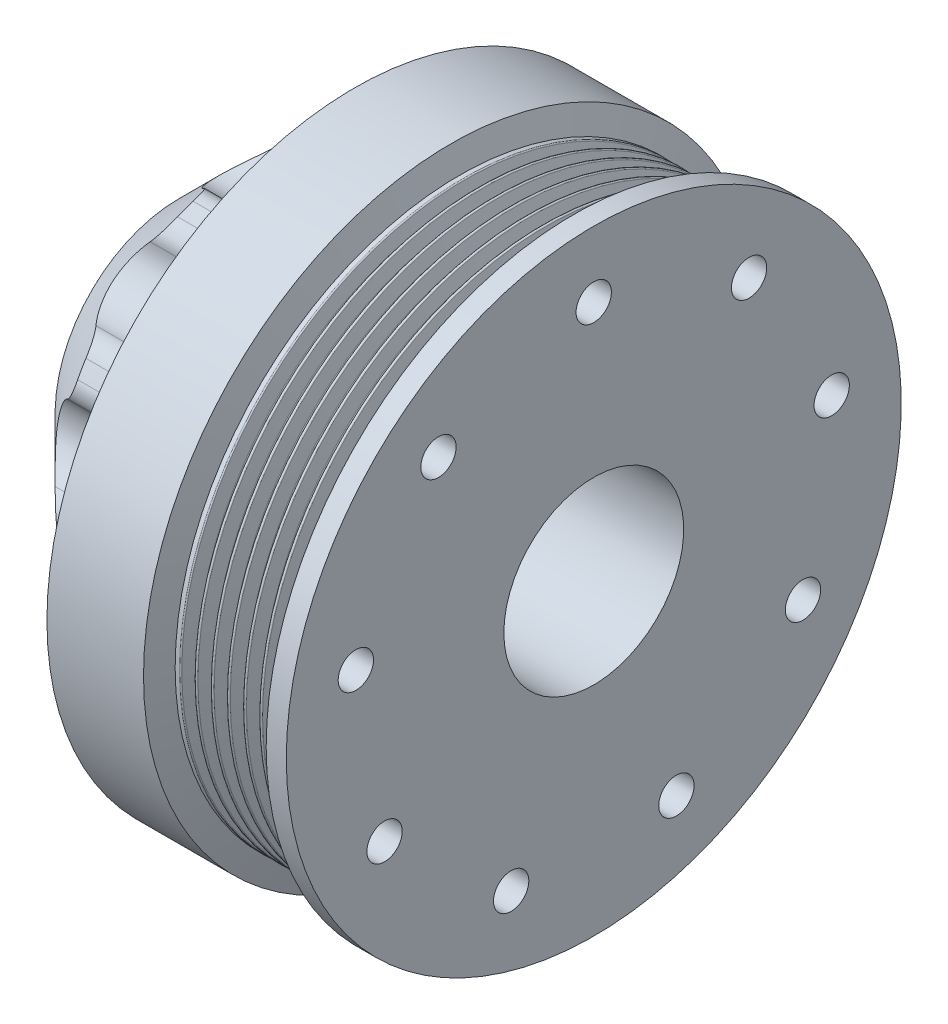
SolidWorks part; units mm, degrees
material "6061-T6 (SS)"
ref_plane "Front Plane" through (0, 0, 0) normal (0, 0, 1) x (1, 0, 0)
ref_plane "Top Plane" through (0, 0, 0) normal (0, 1, 0) x (1, 0, 0)
ref_plane "Right Plane" through (0, 0, 0) normal (1, 0, 0) x (0, 0, -1)
sketch "Sketch1" plane through (0, 0, 0) normal (0, 0, 1) x (1, 0, 0)
  line L0 (0, 0) -> (106.255, 0) construction
  line L1 (-19.05, 13) -> (40.95, 13)
  line L2 (40.95, 13) -> (40.95, 44.45)
  line L3 (40.95, 44.45) -> (6.35, 44.45)
  line L4 (6.35, 44.45) -> (6.35, 28.575)
  line L5 (6.35, 28.575) -> (-19.05, 28.575)
  line L6 (-19.05, 28.575) -> (-19.05, 13)
  line L7 (6.35, 23.3759) -> (6.35, 30.1323) construction
  dimension "D1" = 34.6
  dimension "D2" = 88.9
  dimension "D3" = 26
  dimension "D4" = 25.4
  dimension "D5" = 57.15
revolve "Revolve1" add sketch "Sketch1" angle 360 about L0
sketch "Sketch3" plane through (-19.05, 0, 0) normal (-1, 0, 0) x (0, 0, 1)
  line L0 (0, 0) -> (0, 34.925) construction
  arc A0 (-6.0532, 27.9265) -> (6.0532, 27.9265) centre (0, 29.845) ccw
  circle A1 centre (0, 0) radius 28.575 construction
  arc A2 (6.0532, 27.9265) -> (-6.0532, 27.9265) centre (0, 0) ccw
  point P6 (0, 23.495)
  point P10 (0, 28.575)
  dimension "D1" = 34.925
  dimension "D2" = 5.08
  dimension "D3" = 6.35
extrude "Cut-Extrude1" cut sketch "Sketch3" against normal up to surface (25.4 mm away) up to face at (6.35, 0, 28.575)
fillet "Fillet1" radius 3.175 2 edges at (-6.35, 27.9265, 6.0532) (-6.35, 27.9265, -6.0532)
sketch "Sketch6" plane through (6.35, 0, 0) normal (-1, 0, 0) x (0, 0, 1)
  point P0 (0, 34.925)
hole_wizard "1/4-20 Tapped Hole1" positions "Sketch7" profile "Sketch9" tap size "1/4-20" standard "ANSI Inch" end condition through all
sketch "Sketch7" plane through (6.35, 0, 0) normal (-1, 0, 0) x (0, 0, 1)
  point P0 (0, 34.925)
sketch "Sketch9" plane through (6.35, 34.925, 0) normal (0, 1, 0) x (0, 0, 1)
  line L0 (0, 0) -> (0, 34.6)
  line L1 (0, 34.6) -> (2.5527, 34.6)
  line L2 (2.5527, 34.6) -> (2.5527, 0)
  line L5 (2.5527, 0) -> (0, 0)
  line L11 (0, -6.35) -> (0, 107.95) construction
  dimension "Thru Tap Drill Dia." = 5.1054
  dimension "Thru Tap Drill Depth" = 34.6
pattern_circular "CirPattern1" count 9 over 360 about axis through (6.35, 0, 0) along (-1, 0, 0) of "Cut-Extrude1", "Fillet1", "1/4-20 Tapped Hole1"
sketch "Sketch14" plane through (6.35, 0, 0) normal (-1, 0, 0) x (0, 0, 1)
  line L1 (22.4494, 26.7541) -> (33.8007, 40.2821) construction
  line L2 (0, 34.925) -> (0, 54.7046) construction
  arc A4 (10.6724, 36.5747) -> (15.3343, 34.8779) centre (0, 0) cw
  circle A5 centre (0, 0) radius 44.45 construction
  arc A6 (8.7158, 29.8694) -> (12.523, 28.4836) centre (0, 0) cw
  arc A7 (10.8892, 26.4189) -> (8.6401, 27.2374) centre (0, 0) ccw construction
  arc A8 (12.523, 28.4836) -> (15.3343, 34.8779) centre (13.9286, 31.6808) ccw
  arc A9 (8.7158, 29.8694) -> (10.6724, 36.5747) centre (9.6941, 33.222) cw
  circle A10 centre (22.4494, 26.7541) radius 6.35 construction
  circle A11 centre (0, 34.925) radius 6.35 construction
  dimension "D2" = 6.35
  dimension "D4" = 2.54
  dimension "D1" = 12.7
extrude "Cut-Extrude2" [suppressed] cut sketch "Sketch14" against normal offset from surface (25.075 mm away) 9.525 up to face at (40.95, 26.7541, 25.0021)
pattern_circular "CirPattern2" [suppressed] count 9 over 360 of bodies 109
sketch "Sketch10" plane through (0, 0, 0) normal (0, 0, 1) x (1, 0, 0)
  line L0 (40.95, 44.45) -> (6.35, 44.45) construction
  line L2 (35.9966, 40.9635) -> (35.401, 39.3272)
  line L3 (34.6372, 39.3272) -> (34.0416, 40.9635)
  line L9 (36.1875, 44.45) -> (33.8507, 44.45)
  line L10 (40.95, 44.45) -> (6.35, 44.45) construction
  line L11 (34.0416, 40.9635) -> (35.9966, 40.9635) construction
  line L12 (0, 0) -> (72.0631, 0) construction
  line L13 (36.1875, 41.0972) -> (36.1875, 44.45)
  line L14 (33.8507, 41.0972) -> (33.8507, 44.45)
  line L15 (33.2905, 39.0598) -> (37.1262, 39.0598) construction
  line L16 (32.9874, 42.291) -> (37.178, 42.291) construction
  arc A0 (34.6372, 39.3272) -> (35.401, 39.3272) centre (35.0191, 39.4662) ccw
  arc A1 (35.9966, 40.9635) -> (36.1875, 41.0972) centre (36.1875, 40.894) cw
  arc A2 (34.0416, 40.9635) -> (33.8507, 41.0972) centre (33.8507, 40.894) ccw
  dimension "D4" = 4.7625
  dimension "D2" = 40
  dimension "D5" = 2.0374
  dimension "D6" = 2.3368
  dimension "D7" = 42.291
  dimension "D8" = 1.1938
ref_axis "Axis1" through (40.95, 0, 0) along (-1, 0, 0)
revolve "Cut-Revolve1" cut sketch "Sketch10" angle 360 about axis through (40.95, 0, 0) along (-1, 0, 0)
pattern_linear "LPattern2" count 6 spacing 2.3368 along (-1, 0, 0) of "Cut-Revolve1"
sketch "Sketch23" plane through (0, 0, 0) normal (0, 0, 1) x (1, 0, 0)
  line L0 (36.1875, 41.0972) -> (36.8225, 41.0972)
  line L1 (36.8225, 41.0972) -> (38.0428, 44.45)
  line L2 (40.95, 44.45) -> (36.1875, 44.45) construction
  line L3 (38.0428, 44.45) -> (36.1875, 44.45)
  line L4 (36.1875, 44.45) -> (36.1875, 41.0972)
  line L5 (35.0191, 39.0598) -> (35.0191, 41.518) construction
  line L6 (29.1771, 41.0972) -> (29.1771, 44.846) construction
  line L7 (22.1667, 44.45) -> (22.1667, 41.0972)
  line L8 (20.3114, 44.45) -> (22.1667, 44.45)
  line L9 (21.5317, 41.0972) -> (20.3114, 44.45)
  line L10 (22.1667, 41.0972) -> (21.5317, 41.0972)
  line L11 (40.95, 44.45) -> (36.1875, 44.45) construction
  arc A0 (34.6372, 39.3272) -> (35.401, 39.3272) centre (35.0191, 39.4662) ccw construction
  arc A1 (29.368, 40.9635) -> (28.9862, 40.9635) centre (29.1771, 40.894) ccw construction
  dimension "D1" = 1.8034
  dimension "D2" = 20
revolve "Cut-Revolve3" cut sketch "Sketch23" angle 360 about axis through (40.95, 0, 0) along (-1, 0, 0)
sketch "Sketch11" plane through (0, 0, 0) normal (0, 0, 1) x (1, 0, 0)
  line L1 (6.35, 44.45) -> (-19.05, 44.45)
  line L2 (-19.05, 44.45) -> (-19.05, 17.8611)
  line L3 (-19.05, 13) -> (-19.05, -13) construction
  line L4 (0, 0) -> (-37.8551, 0) construction
  line L5 (-19.05, 17.8611) -> (6.35, 43.2611)
  line L6 (6.35, 43.2611) -> (6.35, 44.45)
  line L7 (6.35, 27.3861) -> (-19.05, 27.3861) construction
  dimension "D1" = 9.525
  dimension "D2" = 45
revolve "Cut-Revolve2" cut sketch "Sketch11" angle 360 about L4
equation "\"D7@Sketch10\"=3.33in/2"
equation "\"D8@Sketch10\"=.094/2"
